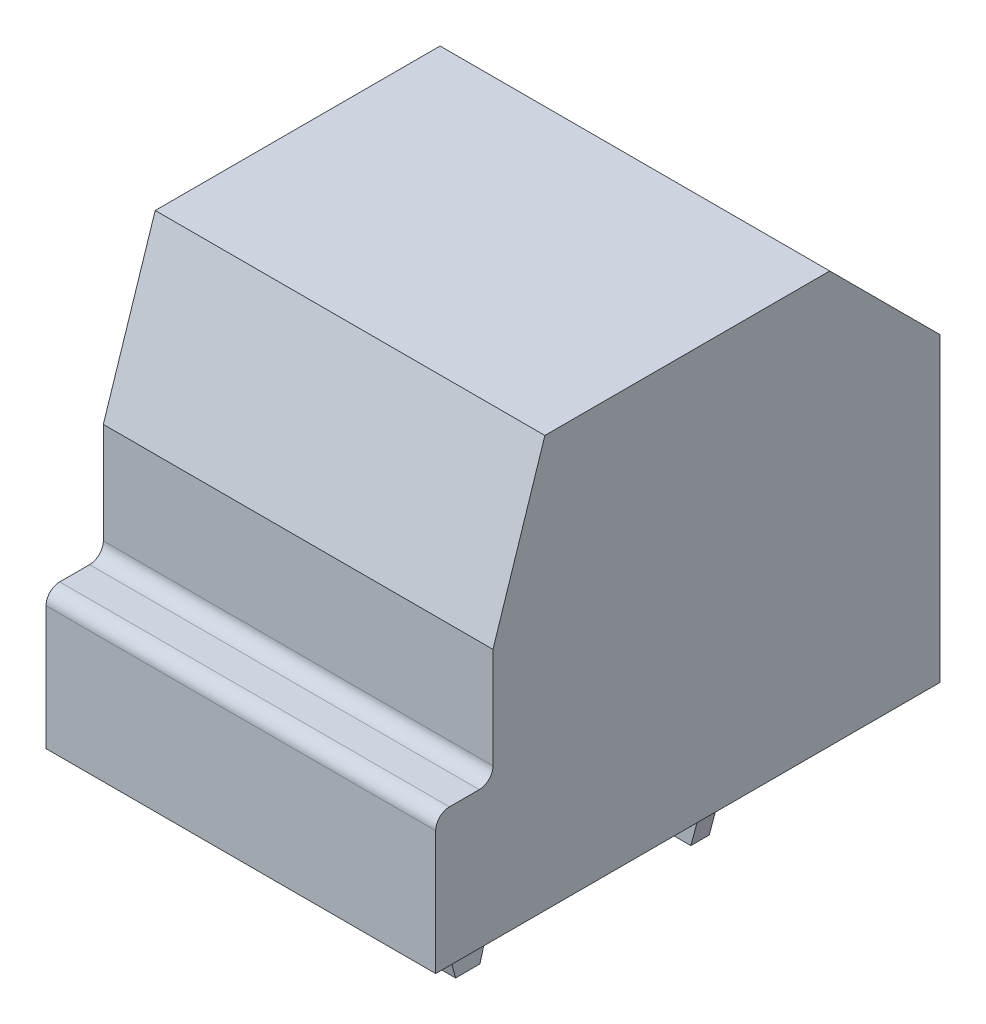
SolidWorks part; units mm, degrees
ref_plane "Front Plane" through (0, 0, 0) normal (0, 0, 1) x (1, 0, 0)
ref_plane "Top Plane" through (0, 0, 0) normal (0, 1, 0) x (1, 0, 0)
ref_plane "Right Plane" through (0, 0, 0) normal (1, 0, 0) x (0, 0, -1)
sketch "Sketch2" plane through (0, 0, 0) normal (1, 0, 0) x (0, 0, -1)
  line L0 (0, 0) -> (11, 0)
  line L5 (11, 0) -> (11, 6.5709)
  line L6 (11, 6.5709) -> (8.5958, 8.975)
  line L7 (8.5958, 8.975) -> (2.3818, 8.975)
  line L8 (2.3818, 8.975) -> (1.25, 5.5)
  line L9 (1.25, 5.5) -> (1.25, 3)
  line L10 (1.25, 3) -> (0, 3)
  line L11 (0, 3) -> (0, 0)
  dimension "D1" = 11
  dimension "D2" = 6.214
  dimension "D3" = 3.4
  dimension "D4" = 2.5
  dimension "D5" = 3
  dimension "D6" = 1.25
extrude "Boss-Extrude2" add sketch "Sketch2" along normal blind 8.5
sketch "Sketch3" plane through (0, 0, 0) normal (0, -1, 0) x (1, 0, 0)
  line L0 (6, -3) -> (8.5, -3) construction
  line L5 (5.8, -3.4) -> (6.2, -3.4)
  line L6 (5.8, -3.4) -> (5.8, -2.6)
  line L7 (5.8, -2.6) -> (6.2, -2.6)
  line L8 (6.2, -3.4) -> (6.2, -2.6)
  line L9 (5.8, -3.4) -> (6.2, -2.6) construction
  line L10 (5.8, -2.6) -> (6.2, -3.4) construction
  line L12 (8.5, 0) -> (8.5, -11) construction
  line L13 (5.6, -7.8) -> (6.4, -7.8)
  line L14 (5.6, -7.8) -> (5.6, -8.2)
  line L15 (5.6, -8.2) -> (6.4, -8.2)
  line L16 (6.4, -7.8) -> (6.4, -8.2)
  line L17 (5.6, -7.8) -> (6.4, -8.2) construction
  line L18 (5.6, -8.2) -> (6.4, -7.8) construction
  line L19 (6, -3) -> (6, -8) construction
  line L20 (6, -3) -> (6, 0) construction
  line L21 (8.5, 0) -> (0, 0) construction
  point P0 (6, -3)
  point P9 (6, -8)
  dimension "D1" = 2.5
  dimension "D2" = 0.8
  dimension "D3" = 0.4
  dimension "D4" = 5
  dimension "D5" = 3
extrude "Boss-Extrude3" add sketch "Sketch3" along normal blind 2.6
chamfer "Chamfer1" distance 0.5 angle 15 4 edges at (6, -2.6, -2.6) (6, -2.6, -3.4) (5.6, -2.6, -8) (6.4, -2.6, -8) first distance on face at (6, -1.3, -2.6) first distance on face at (6, -1.3, -3.4) first distance on face at (5.6, -1.3, -8) first distance on face at (6.4, -1.3, -8)
pattern_linear "LPattern1" count 2 spacing 3.5 along (-1, 0, 0) of "Boss-Extrude3", "Chamfer1"
sketch "Sketch4" plane through (0, 8.7854, -8.7854) normal (0, 0.7071, -0.7071) x (1, 0, 0)
  line L0 (6, -0.2681) -> (6, 3.1319) construction
  line L1 (7.25, 2.6819) -> (4.75, 2.6819)
  line L2 (7.25, 2.6819) -> (7.25, 0.1819)
  line L3 (7.25, 0.1819) -> (4.75, 0.1819)
  line L4 (4.75, 2.6819) -> (4.75, 0.1819)
  line L5 (7.25, 2.6819) -> (4.75, 0.1819) construction
  line L6 (7.25, 0.1819) -> (4.75, 2.6819) construction
  line L7 (8.5, -0.2681) -> (0, -0.2681) construction
  line L8 (8.5, 3.1319) -> (0, 3.1319) construction
  line L9 (6, 1.4319) -> (8.5, 1.4319) construction
  line L10 (8.5, 3.1319) -> (8.5, -0.2681) construction
  point P0 (6, 1.4319)
  point P12 (6, 1.4319)
  dimension "D1" = 2.5
  dimension "D2" = 2.5
  dimension "D3" = 2.5
extrude "Cut-Extrude1" cut sketch "Sketch4" against normal blind 2
chamfer "Chamfer2" distance 1.1 angle 25 4 edges at (6, 5.4749, -9.2676) (7.25, 6.3588, -8.3837) (6, 7.2426, -7.4998) (4.75, 6.3588, -8.3837) first distance on face at (6, 6.182, -9.9747) first distance on face at (7.25, 7.0659, -9.0908) first distance on face at (6, 7.9497, -8.2069) first distance on face at (4.75, 7.0659, -9.0908)
fillet "Fillet1" radius 0.6 8 edges at (7.25, 6.5709, -10.3636) (4.75, 6.5709, -10.3636) (4.75, 8.3387, -8.5958) (7.25, 8.3387, -8.5958) (6.9935, 6.0451, -9.4751) (5.0065, 6.0451, -9.4751) (5.0065, 7.4502, -8.0701) (6.9935, 7.4502, -8.0701)
pattern_linear "LPattern2" count 2 spacing 3.5 along (-1, 0, 0) of "Fillet1", "Chamfer2", "Cut-Extrude1"
fillet "Fillet2" radius 0.3 2 edges at (4.25, 3, -1.25) (4.25, 3, 0)
